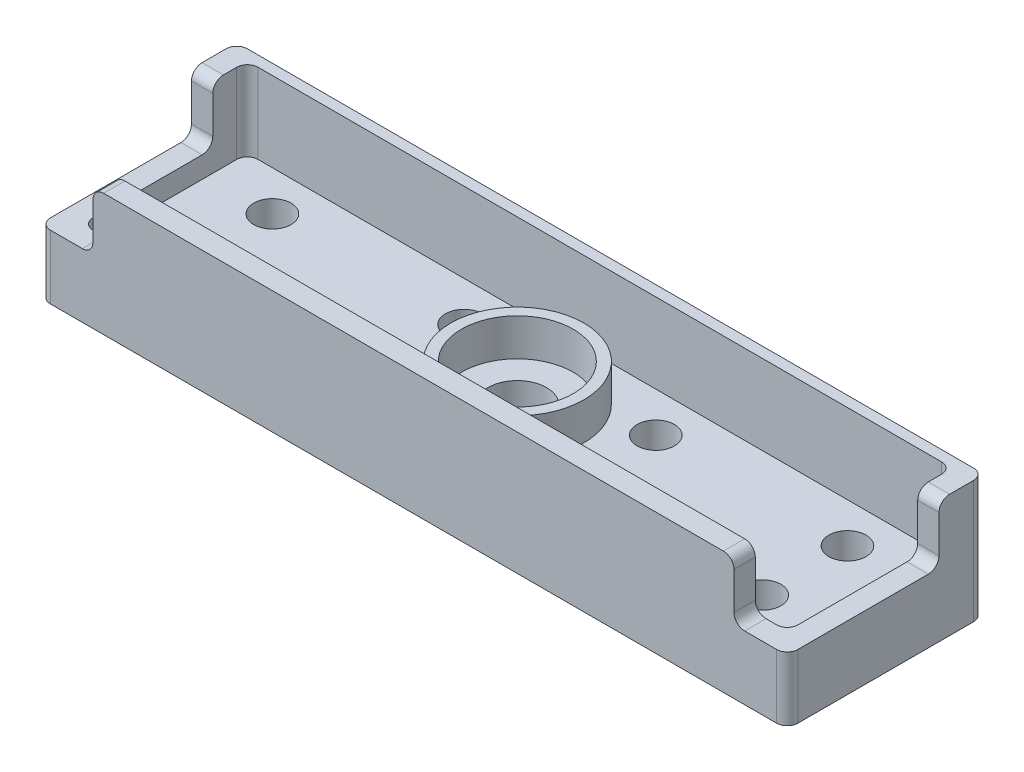
SolidWorks part; units mm, degrees
material "Delrin 2700 NC010, Low Viscosity Acetal Copolymer (SS)"
ref_plane "Front Plane" through (0, 0, 0) normal (0, 0, 1) x (1, 0, 0)
ref_plane "Top Plane" through (0, 0, 0) normal (0, 1, 0) x (1, 0, 0)
ref_plane "Right Plane" through (0, 0, 0) normal (1, 0, 0) x (0, 0, -1)
sketch "Sketch1" plane through (0, 0, 0) normal (0, 1, 0) x (1, 0, 0)
  line L1 (-35.1, -9.25) -> (0, -9.25)
  line L2 (-35.1, -9.25) -> (-35.1, 9.25)
  line L3 (-35.1, 9.25) -> (0, 9.25)
  line L4 (0, -9.25) -> (0, 9.25)
  line L5 (-35.1, -9.25) -> (0, 9.25) construction
  line L6 (-35.1, 9.25) -> (0, -9.25) construction
  point P0 (-17.55, 0)
  point P8 (0, 0)
  dimension "D1" = 35.1
  dimension "D2" = 18.5
extrude "Boss-Extrude1" add sketch "Sketch1" along normal blind 11.5
shell "Shell1" [suppressed] thickness 1
sketch "Sketch7" plane through (0, 11.5, 0) normal (0, 1, 0) x (1, 0, 0)
  line L0 (0, -9.25) -> (0, 9.25) construction
  line L1 (0, -7.25) -> (-33.1, -7.25)
  line L2 (0, -7.25) -> (0, 8.25)
  line L3 (0, 8.25) -> (-33.1, 8.25)
  line L4 (-33.1, -7.25) -> (-33.1, 8.25)
  line L5 (-35.1, -9.25) -> (0, -9.25) construction
  line L6 (0, 9.25) -> (-35.1, 9.25) construction
  line L7 (-35.1, 9.25) -> (-35.1, -9.25) construction
  dimension "D1" = 2
  dimension "D2" = 1
  dimension "D3" = 2
extrude "Cut-Extrude5" cut sketch "Sketch7" against normal offset from surface (7.5 mm away) 4 up to face at (-17.55, 0, 0)
sketch "Sketch2" plane through (0, 0, 0) normal (0, 1, 0) x (-1, 0, 0)
  line L0 (27, 3.5) -> (9, 3.5) construction
  line L2 (27, 3.5) -> (27, -4.5) construction
  line L3 (27, -4.5) -> (9, -4.5) construction
  line L4 (9, -4.5) -> (9, 3.5) construction
  line L5 (27, -0.5) -> (18.8977, -0.5) construction
  line L6 (17.55, -9.25) -> (17.55, 9.25) construction
  line L7 (0, 7.25) -> (0, -8.25) construction
  line L8 (27, -0.5) -> (0, -0.5) construction
  line L9 (0, -9.25) -> (35.1, -9.25) construction
  line L10 (35.1, 9.25) -> (0, 9.25) construction
  circle A0 centre (27, 3.5) radius 1.75
  circle A1 centre (9, 3.5) radius 1.75
  circle A2 centre (27, -4.5) radius 1.75
  circle A3 centre (9, -4.5) radius 1.75
  circle A5 centre (27, 3.5) radius 2.5 construction
  circle A6 centre (27, -4.5) radius 2.5 construction
  circle A7 centre (9, -4.5) radius 2.5 construction
  circle A8 centre (9, 3.5) radius 2.5 construction
  dimension "D1" = 3.5
  dimension "D4" = 9
  dimension "D5" = 5
  dimension "D2" = 18
  dimension "D3" = 8
extrude "Cut-Extrude1" cut sketch "Sketch2" along normal through all
sketch "Sketch3" [suppressed] plane through (0, 5, 0) normal (0, 1, 0) x (1, 0, 0)
  line L1 (-2.9573, -5.1559) -> (2.9865, -5.139)
  line L2 (2.9865, -5.139) -> (5.9438, 0.0169)
  line L3 (5.9438, 0.0169) -> (2.9573, 5.1559)
  line L4 (2.9573, 5.1559) -> (-2.9865, 5.139)
  line L5 (-2.9865, 5.139) -> (-5.9438, -0.0169)
  line L6 (-5.9438, -0.0169) -> (-2.9573, -5.1559)
  circle A0 centre (0, 0) radius 2.6 construction
  circle A1 centre (0, 0) radius 5.1475 construction
  dimension "D1" = 5.2
extrude "Cut-Extrude2" [suppressed] cut sketch "Sketch3" against normal blind 0.5
sketch "Sketch4" plane through (-35.1, 0, 0) normal (-1, 0, 0) x (0, 0, 1)
  line L0 (-9.25, 11.5) -> (9.25, 11.5) construction
  line L1 (-5, 11.5) -> (9.25, 11.5)
  line L3 (-5, 6) -> (9.25, 6)
  line L4 (9.25, 11.5) -> (9.25, 6)
  line L5 (0, 6) -> (0, 0) construction
  line L11 (-9.25, 0) -> (9.25, 0) construction
  line L12 (-5, 6) -> (-5, 11.5)
  dimension "D1" = 5
  dimension "D2" = 5.5
extrude "Cut-Extrude3" cut sketch "Sketch4" against normal offset from surface (5 mm away) 3 up to face at (-33.1, 7.75, -0.5) offset beyond the face yes
mirror "Mirror1" about plane through (0, 0, 0) normal (1, 0, 0) of bodies 105
sketch "Sketch5" plane through (0, 0, 0) normal (0, 1, 0) x (1, 0, 0)
  line L0 (33.1, 0.5) -> (0, 0.5) construction
  line L1 (33.1, 8.25) -> (33.1, -7.25) construction
  line L4 (0, 0.5) -> (0, 0) construction
  circle A0 centre (0, 0.5) radius 2.75
  dimension "D1" = 5.5
extrude "Cut-Extrude4" cut sketch "Sketch5" along normal through all
sketch "Sketch6" plane through (0, 4, 0) normal (0, 1, 0) x (1, 0, 0)
  circle A0 centre (0, 0.5) radius 6.25
  circle A1 centre (0, 0.5) radius 5.25
  circle A2 centre (0, 0.5) radius 2.75 construction
  dimension "D1" = 10.5
  dimension "D2" = 1
extrude "Boss-Extrude2" add sketch "Sketch6" along normal blind 3.5
fillet "Fillet3" radius 1 8 edges at (30.1, 6, 8.25) (-30.1, 6, 8.25) (30.1, 11.5, 8.25) (-30.1, 11.5, 8.25) (34.1, 11.5, -5) (34.1, 6, -5) (-34.1, 11.5, -5) (-34.1, 6, -5)
fillet "Fillet4" [suppressed] radius 0.5
fillet "Fillet5" [suppressed] radius 0.5
fillet "Fillet6" radius 1 8 edges at (35.1, 5.75, -9.25) (-35.1, 5.75, -9.25) (-35.1, 3, 9.25) (35.1, 3, 9.25) (-33.1, 5, 7.25) (-33.1, 7.75, -8.25) (33.1, 7.75, -8.25) (33.1, 5, 7.25)
fillet "Fillet7" [suppressed] radius 1
fillet "Fillet8" [suppressed] radius 1
